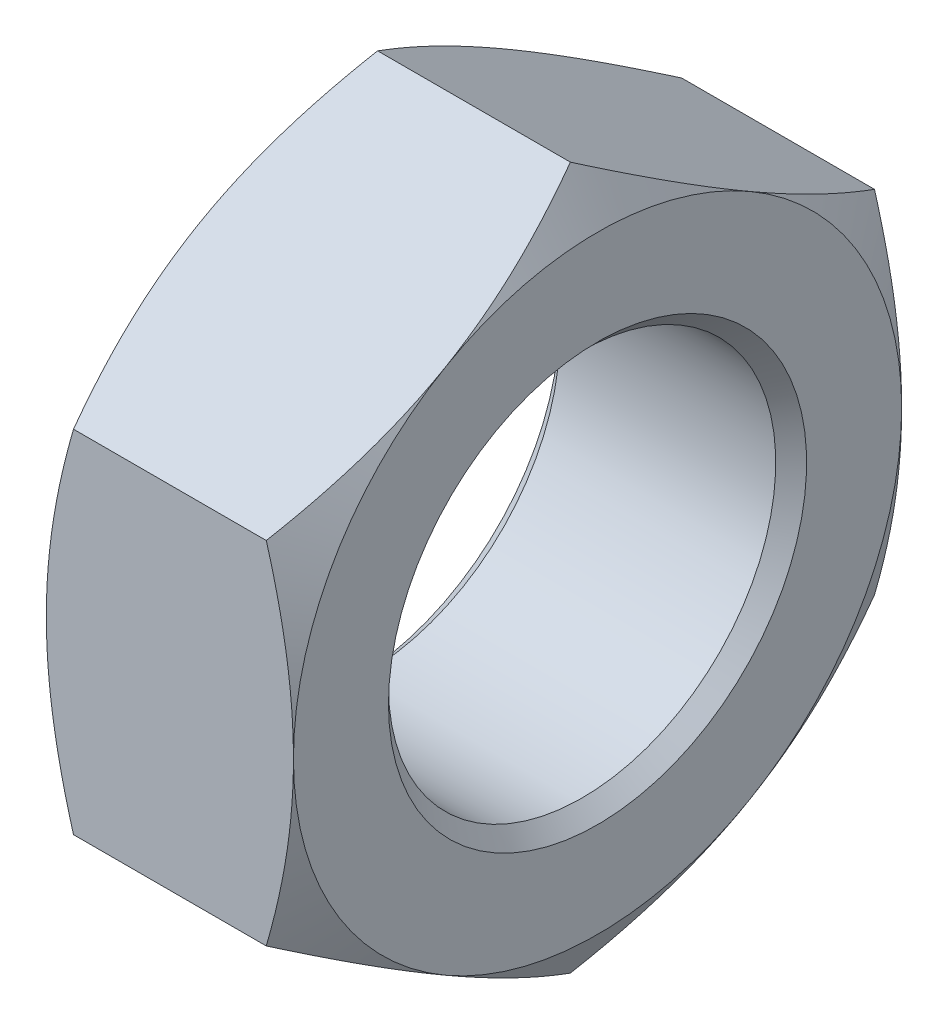
SolidWorks part; units mm, degrees
material "A3钢"
ref_plane "前视基准面" through (0, 0, 0) normal (0, 0, 1) x (1, 0, 0)
ref_plane "上视基准面" through (0, 0, 0) normal (0, 1, 0) x (1, 0, 0)
ref_plane "右视基准面" through (0, 0, 0) normal (1, 0, 0) x (0, 0, -1)
sketch "草图1" plane through (0, 0, 0) normal (0, 0, 1) x (1, 0, 0)
  line L0 (0, 0) -> (0, 16)
  line L1 (0, 16) -> (1.8475, 19.2)
  line L2 (1.8475, 19.2) -> (11.1525, 19.2)
  line L3 (11.1525, 19.2) -> (13, 16)
  line L4 (13, 16) -> (13, 0)
  line L5 (13, 0) -> (0, 0)
  line L6 (13, 0) -> (0, 0) construction
revolve "旋转1" add sketch "草图1" angle 360 about L6 reverse direction yes
sketch "草图2" plane through (0, 0, 0) normal (1, 0, 0) x (0, 0, -1)
  line L0 (-32, 32) -> (-32, -32)
  line L1 (-32, -32) -> (32, -32)
  line L2 (32, -32) -> (32, 32)
  line L3 (32, 32) -> (-32, 32)
  line L4 (-16, -9.2376) -> (0, -18.4752)
  line L5 (0, -18.4752) -> (16, -9.2376)
  line L6 (16, -9.2376) -> (16, 9.2376)
  line L7 (16, 9.2376) -> (0, 18.4752)
  line L8 (0, 18.4752) -> (-16, 9.2376)
  line L9 (-16, 9.2376) -> (-16, -9.2376)
extrude "切除-拉伸1" cut sketch "草图2" along normal blind 26
sketch "草图3" plane through (0, 0, 0) normal (0, 0, 1) x (1, 0, 0)
  line L0 (0, 0) -> (0, 11)
  line L1 (0, 11) -> (0.812, 10.188)
  line L2 (0.812, 10.188) -> (12.188, 10.188)
  line L3 (12.188, 10.188) -> (13, 11)
  line L4 (13, 11) -> (13, 0)
  line L5 (13, 0) -> (0, 0)
  line L6 (13, 0) -> (0, 0) construction
revolve "切除-旋转1" cut sketch "草图3" angle 360 about L6 reverse direction yes
cosmetic thread "装饰螺纹线1" parameters "D1"=13, "D2"=22
ref_plane "基准面1" through (6.5, 0, 0) normal (1, 0, 0) x (0, 0, -1)
ref_plane "IP_RN XY" through (6.5, 0, 0) normal (1, 0, 0) x (0, 0, -1)
ref_plane "IP_RN XZ" through (0, 0, 0) normal (0, -1, 0) x (-1, 0, 0)
ref_plane "IP_RN YZ" through (0, 0, 0) normal (0, 0, -1) x (-1, 0, 0)
ref_axis "IP_RN X" through (6.5, 0, 80.9) along (0, 0, -1)
ref_axis "IP_RN Y" through (6.5, -50, 0) along (0, 1, 0)
ref_axis "IP_RN Z" through (80.9, 0, 0) along (-1, 0, 0)
sketch3d "IP_RN"
  point P0 (6.5, 0, 0)
